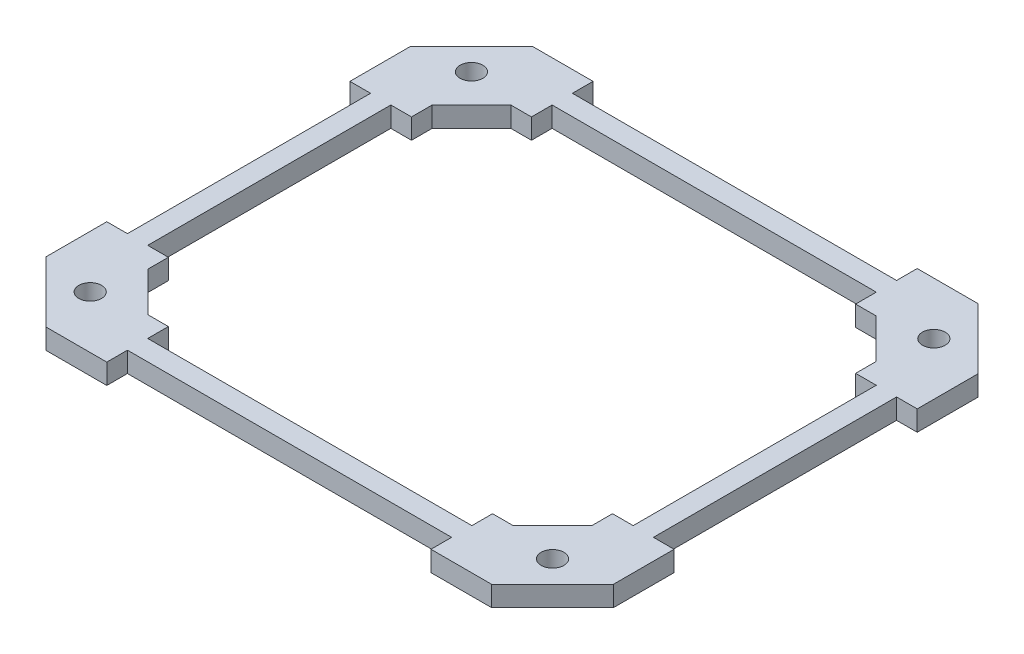
SolidWorks part; units mm, degrees
material "Rubber"
ref_plane "Front Plane" through (0, 0, 0) normal (0, 0, 1) x (1, 0, 0)
ref_plane "Top Plane" through (0, 0, 0) normal (0, 1, 0) x (1, 0, 0)
ref_plane "Right Plane" through (0, 0, 0) normal (1, 0, 0) x (0, 0, -1)
sketch "Sketch1" plane through (0, 0, 0) normal (0, 1, 0) x (1, 0, 0)
  line L0 (-57.15, -56.896) -> (-69.596, -44.45) construction
  line L1 (-69.596, -44.45) -> (-69.596, -38.1) construction
  line L2 (-69.596, -38.1) -> (-88.9, -38.1) construction
  line L3 (-88.9, -38.1) -> (-88.9, -57.15) construction
  line L4 (-88.9, -57.15) -> (-69.85, -76.2) construction
  line L5 (-69.85, -76.2) -> (-50.8, -76.2) construction
  line L6 (-50.8, -76.2) -> (-50.8, -56.896) construction
  line L7 (-50.8, -56.896) -> (-57.15, -56.896) construction
  line L9 (-82.423, 38.1) -> (-82.423, -38.1) construction
  line L11 (-76.073, -38.1) -> (-76.073, 38.1) construction
  line L13 (50.8, -63.373) -> (-50.8, -63.373) construction
  line L15 (-50.8, -69.723) -> (50.8, -69.723) construction
  line L16 (69.596, -44.45) -> (57.15, -56.896) construction
  line L17 (57.15, -56.896) -> (50.8, -56.896) construction
  line L18 (50.8, -56.896) -> (50.8, -76.2) construction
  line L19 (50.8, -76.2) -> (69.85, -76.2) construction
  line L20 (69.85, -76.2) -> (88.9, -57.15) construction
  line L21 (88.9, -57.15) -> (88.9, -38.1) construction
  line L22 (88.9, -38.1) -> (69.596, -38.1) construction
  line L23 (69.596, -38.1) -> (69.596, -44.45) construction
  line L25 (76.073, 38.1) -> (76.073, -38.1) construction
  line L27 (82.423, -38.1) -> (82.423, 38.1) construction
  line L29 (-50.8, 63.373) -> (50.8, 63.373) construction
  line L31 (50.8, 69.723) -> (-50.8, 69.723) construction
  line L32 (57.15, 56.896) -> (69.596, 44.45) construction
  line L33 (69.596, 44.45) -> (69.596, 38.1) construction
  line L34 (69.596, 38.1) -> (88.9, 38.1) construction
  line L35 (88.9, 38.1) -> (88.9, 57.15) construction
  line L36 (88.9, 57.15) -> (69.85, 76.2) construction
  line L37 (69.85, 76.2) -> (50.8, 76.2) construction
  line L38 (50.8, 76.2) -> (50.8, 56.896) construction
  line L39 (50.8, 56.896) -> (57.15, 56.896) construction
  line L40 (-69.596, 44.45) -> (-57.15, 56.896) construction
  line L41 (-57.15, 56.896) -> (-50.8, 56.896) construction
  line L42 (-50.8, 56.896) -> (-50.8, 76.2) construction
  line L43 (-50.8, 76.2) -> (-69.85, 76.2) construction
  line L44 (-69.85, 76.2) -> (-88.9, 57.15) construction
  line L45 (-88.9, 57.15) -> (-88.9, 38.1) construction
  line L46 (-88.9, 38.1) -> (-69.596, 38.1) construction
  line L47 (-69.596, 38.1) -> (-69.596, 44.45) construction
  line L48 (-57.15, -56.896) -> (-69.596, -44.45)
  line L49 (-69.596, -44.45) -> (-69.596, -38.1)
  line L50 (-69.596, -38.1) -> (-76.073, -38.1)
  line L51 (-88.9, -38.1) -> (-88.9, -57.15)
  line L52 (-88.9, -57.15) -> (-69.85, -76.2)
  line L53 (-69.85, -76.2) -> (-50.8, -76.2)
  line L54 (-50.8, -76.2) -> (-50.8, -69.723)
  line L55 (-50.8, -56.896) -> (-57.15, -56.896)
  line L57 (-82.423, 38.1) -> (-82.423, -38.1)
  line L59 (-76.073, -38.1) -> (-76.073, 38.1)
  line L61 (50.8, -63.373) -> (-50.8, -63.373)
  line L63 (-50.8, -69.723) -> (50.8, -69.723)
  line L64 (69.596, -44.45) -> (57.15, -56.896)
  line L65 (57.15, -56.896) -> (50.8, -56.896)
  line L66 (50.8, -56.896) -> (50.8, -63.373)
  line L67 (50.8, -76.2) -> (69.85, -76.2)
  line L68 (69.85, -76.2) -> (88.9, -57.15)
  line L69 (88.9, -57.15) -> (88.9, -38.1)
  line L70 (88.9, -38.1) -> (82.423, -38.1)
  line L71 (69.596, -38.1) -> (69.596, -44.45)
  line L73 (76.073, 38.1) -> (76.073, -38.1)
  line L75 (82.423, -38.1) -> (82.423, 38.1)
  line L77 (-50.8, 63.373) -> (50.8, 63.373)
  line L79 (50.8, 69.723) -> (-50.8, 69.723)
  line L80 (57.15, 56.896) -> (69.596, 44.45)
  line L81 (69.596, 44.45) -> (69.596, 38.1)
  line L82 (69.596, 38.1) -> (76.073, 38.1)
  line L83 (88.9, 38.1) -> (88.9, 57.15)
  line L84 (88.9, 57.15) -> (69.85, 76.2)
  line L85 (69.85, 76.2) -> (50.8, 76.2)
  line L86 (50.8, 76.2) -> (50.8, 69.723)
  line L87 (50.8, 56.896) -> (57.15, 56.896)
  line L88 (-69.596, 44.45) -> (-57.15, 56.896)
  line L89 (-57.15, 56.896) -> (-50.8, 56.896)
  line L90 (-50.8, 56.896) -> (-50.8, 63.373)
  line L91 (-50.8, 76.2) -> (-69.85, 76.2)
  line L92 (-69.85, 76.2) -> (-88.9, 57.15)
  line L93 (-88.9, 57.15) -> (-88.9, 38.1)
  line L94 (-88.9, 38.1) -> (-82.423, 38.1)
  line L95 (-69.596, 38.1) -> (-69.596, 44.45)
  line L96 (50.8, 63.373) -> (50.8, 56.896)
  line L97 (82.423, 38.1) -> (88.9, 38.1)
  line L98 (76.073, -38.1) -> (69.596, -38.1)
  line L99 (50.8, -69.723) -> (50.8, -76.2)
  line L100 (-50.8, 69.723) -> (-50.8, 76.2)
  line L101 (-76.073, 38.1) -> (-69.596, 38.1)
  line L102 (-82.423, -38.1) -> (-88.9, -38.1)
  line L103 (-50.8, -63.373) -> (-50.8, -56.896)
extrude "Boss-Extrude1" add sketch "Sketch1" along normal blind 6.35
hole_wizard "1/4 Clearance Hole1" positions "Sketch2" profile "Sketch3" hole size "1/4" standard "ANSI Inch" end condition through all
sketch "Sketch2" plane through (0, 0, 0) normal (0, -1, 0) x (-1, 0, 0)
  point P0 (-72.4527, 59.7527)
  point P3 (72.4527, 59.7527)
  point P6 (72.4527, -59.7527)
  point P9 (-72.4527, -59.7527)
  point P12 (0, 0)
sketch "Sketch3" plane through (72.4527, 0, -59.7527) normal (1, 0, 0) x (0, 0, -1)
  line L0 (0, 0) -> (0, 6.35)
  line L1 (0, 6.35) -> (3.5712, 6.35)
  line L2 (3.5712, 6.35) -> (3.5712, 0)
  line L5 (3.5712, 0) -> (0, 0)
  line L11 (0, -6.35) -> (0, 107.95) construction
  dimension "Thru Hole Dia." = 7.1425
  dimension "Thru Hole Depth" = 6.35
